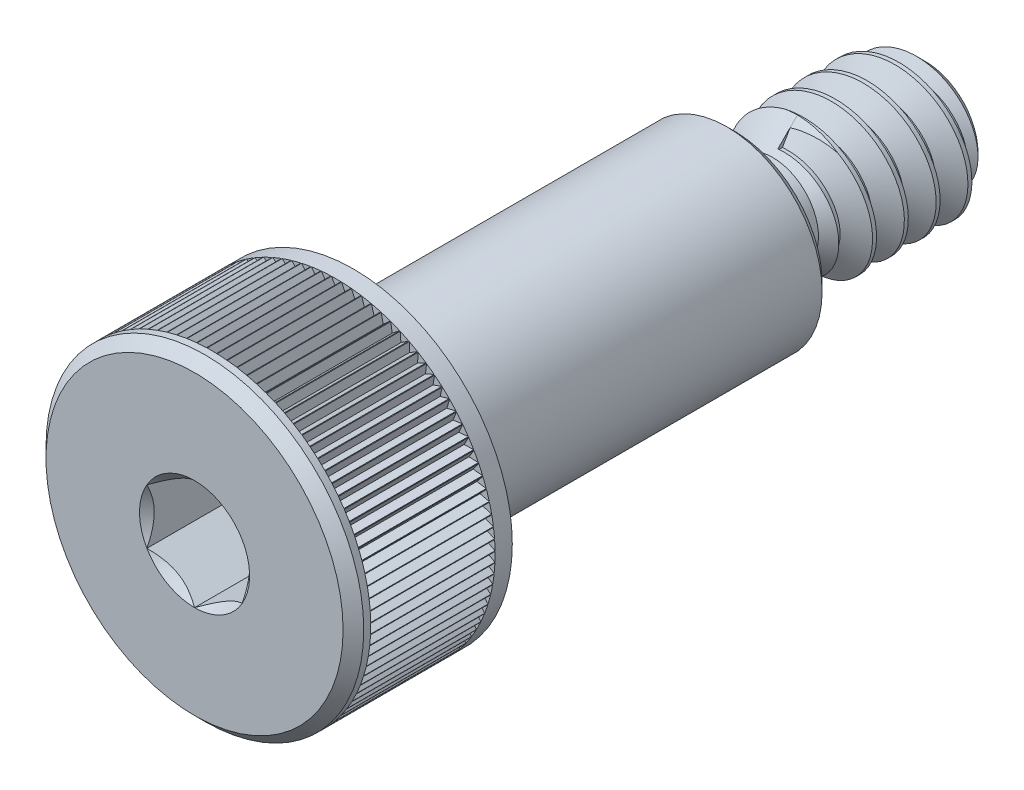
SolidWorks part; units mm, degrees
other "DetailItem1"
other "DetailItem2"
other "DetailItem5"
other "DetailItem6"
ref_plane "Front" through (0, 0, 0) normal (0, 0, 1) x (1, 0, 0)
ref_plane "Top" through (0, 0, 0) normal (0, 1, 0) x (1, 0, 0)
ref_plane "Right" through (0, 0, 0) normal (1, 0, 0) x (0, 0, -1)
sketch "Sketch1" plane through (0, 0, 0) normal (1, 0, 0) x (0, 0, -1)
  line L0 (0, 3.9687) -> (3.9687, 3.9688) construction
  line L1 (3.9687, 3.9688) -> (3.9687, 2.1828) construction
  line L2 (4.9609, 2.3812) -> (13.4938, 2.3812) construction
  line L3 (4.9609, -2.3812) -> (13.4938, -2.3813) construction
  line L4 (13.4938, 1.7526) -> (18.2563, 1.7526) construction
  line L5 (18.2563, 1.7526) -> (18.2563, 0) construction
  line L6 (13.4938, 0) -> (0, 0) construction
  line L7 (0, 0) -> (0, 3.9687) construction
  line L8 (0, 3.9687) -> (0, -3.9688) construction
  line L9 (18.2563, 1.7526) -> (18.2563, -1.7526) construction
  line L10 (13.4938, 2.3812) -> (13.4938, -2.3813) construction
  line L11 (18.2563, -1.7526) -> (16.5785, -1.7526) construction
  line L12 (13.4938, 2.3812) -> (13.4938, 0) construction
  line L13 (3.9687, 2.1828) -> (4.7625, 2.1828) construction
  line L14 (4.7625, 2.1828) -> (4.9609, 2.3812) construction
  line L15 (18.2563, 0) -> (13.4938, 0) construction
  line L16 (4.7625, -2.1828) -> (4.9609, -2.3812) construction
  line L17 (3.9688, -2.1828) -> (4.7625, -2.1828) construction
  line L18 (0, -3.9688) -> (3.9688, -3.9688) construction
  line L19 (3.9688, -3.9688) -> (3.9688, -2.1828) construction
  line L20 (18.2563, 2.3813) -> (17.0656, 2.3813) construction
  line L21 (18.2563, -2.3812) -> (17.0656, -2.3812) construction
  line L22 (18.2563, 0) -> (23.0188, 0) construction
  line L23 (8.7313, 0) -> (8.7313, 3.9688) construction
  line L24 (18.2563, -2.3812) -> (18.2563, 2.3813) construction
  line L25 (0, -1.1906) -> (0, 1.1906) construction
  line L26 (18.2066, 1.8385) -> (19.0004, 1.8385) construction
  line L27 (19.0004, 1.8385) -> (18.6035, 1.1511) construction
  line L28 (18.6035, 1.1511) -> (18.2066, 1.8385) construction
  line L29 (18.6035, 1.1511) -> (18.6035, 1.237) construction
  line L30 (18.6035, 1.8385) -> (18.6035, 1.7526) construction
  line L31 (18.9508, 1.7526) -> (18.2563, 1.7526) construction
  line L32 (18.5539, 1.237) -> (18.6531, 1.237) construction
  line L33 (18.6035, 1.7956) -> (18.9756, 1.7956) construction
  line L34 (18.6035, 1.7956) -> (18.2314, 1.7956) construction
  line L35 (4.9609, 2.3812) -> (4.9609, -2.3812) construction
  line L36 (13.2953, 2.3813) -> (13.4938, 2.1828) construction
  line L37 (13.2953, 2.3813) -> (13.2953, 0) construction
  point P2 (4.2069, 0)
  point P8 (17.0656, -1.7526)
  point P12 (13.4938, 0)
  point P15 (13.2556, 0)
  point P31 (4.6593, 0)
  point P32 (12.8032, 0)
  point P34 (18.2563, 0)
  point P37 (0, 0)
  dimension "Head Dia" = 7.9375
  dimension "Head Ht" = 3.9688
  dimension "Thread Lg" = 4.7625
  dimension "Thread Dia" = 3.5052
  dimension "Shoulder Dia" = 4.7625
  dimension "D1" = 1.1906
  dimension "D2" = 1.6778
  dimension "D3" = 135
  dimension "D4" = 0.7937
  dimension "D5" = 0.1984
  dimension "D6" = 4.7625
  dimension "D7" = 9.0487
  dimension "D8" = 8.1439
  dimension "Hex" = 2.3813
  dimension "Pitch" = 0.7937
  dimension "D9" = 0.0992
  dimension "Shoulder Lg" = 9.525
  dimension "D10" = 45
sketch "Sketch13" plane through (0, 0, 0) normal (1, 0, 0) x (0, 0, -1)
  line L0 (0, 0) -> (0, 3.9687)
  line L1 (0, 3.9687) -> (3.9687, 3.9688)
  line L2 (3.9687, 3.9688) -> (3.9687, 2.1828)
  line L3 (3.9687, 2.1828) -> (4.7625, 2.1828)
  line L4 (13.4938, 0) -> (13.4938, 2.1828)
  line L5 (4.7625, 2.1828) -> (4.9609, 2.3813)
  line L7 (13.4938, 2.3812) -> (13.4938, 0) construction
  line L8 (13.4938, 2.3812) -> (13.4938, -2.3813) construction
  line L9 (13.4938, 0) -> (0, 0) construction
  line L10 (13.4938, 2.1828) -> (13.2953, 2.3812)
  line L12 (4.9609, 2.3813) -> (13.2953, 2.3812)
  line L13 (0, 0) -> (13.4938, 0)
  line L14 (4.9609, 2.3812) -> (13.4938, 2.3812) construction
  line L18 (18.2563, 2.3813) -> (18.2563, -2.3812) construction
  dimension "D1" = 9.525
  dimension "D2" = 45
  dimension "D3" = 4.7625
revolve "Revolve1" add sketch "Sketch13" angle 360 about L9
sketch "Sketch12" plane through (0, 0, -13.4938) normal (0, 0, -1) x (-1, 0, 0)
  circle A0 centre (0, 0) radius 1.7526
extrude "Boss-Extrude1" add sketch "Sketch12" along normal up to vertex (4.7625 mm away) up to point (0, 0, -18.2563)
ref_plane "Plane1" through (0, 0, -18.2563) normal (0, 0, 1) x (1, 0, 0)
sketch "Sketch3" plane through (0, 0, -18.2563) normal (0, 0, 1) x (1, 0, 0)
  circle A0 centre (0, 0) radius 1.7526
sketch "Sketch5" plane through (0, 0, 0) normal (1, 0, 0) x (0, 0, -1)
  line L0 (13.4938, 1.7526) -> (15.0597, 1.7526)
  line L1 (15.0597, 1.7526) -> (14.4463, 1.1392)
  line L2 (14.4463, 1.1392) -> (13.4938, 1.1392)
  line L3 (13.4938, 1.7526) -> (13.4938, 1.1392)
  line L4 (13.4938, 1.7526) -> (18.2563, 1.7526) construction
  line L5 (13.4938, 2.3812) -> (13.4938, 0) construction
  line L6 (13.4938, 2.3812) -> (13.4938, -2.3813) construction
  line L7 (18.2563, 0) -> (13.4938, 0) construction
  line L8 (18.2563, -1.7526) -> (18.2563, 1.7526) construction
  dimension "D4" = 0.9525
  dimension "D1" = 45
  dimension "D2" = 3.81
  dimension "D3" = 1.1392
revolve "Cut-Revolve1" cut sketch "Sketch5" angle 360 mid plane about L6
chamfer "Chamfer1" distance 0.4381 angle 45 1 edges at (-1.7526, 0, -18.2563)
chamfer "Chamfer2" distance 0.258 angle 45 1 edges at (-3.9687, 0, 0)
fillet "Fillet1" radius 0.1984 1 edges at (0, 1.1392, -13.4938)
sketch "Sketch10" plane through (0, 0, 0) normal (1, 0, 0) x (0, 0, -1)
  line L0 (0.258, 0) -> (3.7108, 0) construction
  line L1 (3.9687, -3.9688) -> (3.9687, 3.9688) construction
  line L2 (0.258, -3.9687) -> (0.258, 3.9687) construction
  line L3 (0.258, 0) -> (0, 0) construction
  line L4 (3.7108, 0) -> (3.9687, 0) construction
  point P6 (1.9844, 0)
  dimension "D1" = 3.4528
ref_plane "Plane2" through (0, 0, -1.9844) normal (0, 0, 1) x (1, 0, 0)
sketch "Sketch8" plane through (0, 0, 0) normal (0, 0, 1) x (1, 0, 0)
  line L1 (1.1906, 0.6874) -> (0, 1.3748)
  line L2 (0, 1.3748) -> (-1.1906, 0.6874)
  line L3 (-1.1906, 0.6874) -> (-1.1906, -0.6874)
  line L4 (-1.1906, -0.6874) -> (0, -1.3748)
  line L5 (0, -1.3748) -> (1.1906, -0.6874)
  line L6 (1.1906, -0.6874) -> (1.1906, 0.6874)
  circle A0 centre (0, 0) radius 1.1906 construction
extrude "Cut-Extrude2" cut sketch "Sketch8" against normal blind 1.9844
sketch "Sketch9" plane through (0, 0, 0) normal (0, 0, 1) x (1, 0, 0)
  circle A0 centre (0, 0) radius 1.3748
extrude "Cut-Extrude4" cut sketch "Sketch9" against normal blind 1.9844 draft 45
sketch "Sketch16" plane through (0, 0, 0) normal (0, 1, 0) x (1, 0, 0)
  line L0 (0, 8.7313) -> (-2.3812, 8.7313) construction
  line L1 (-2.3812, 13.2953) -> (-2.3812, 4.9609) construction
  line L2 (0, 12.8032) -> (-2.3812, 12.8032) construction
  line L3 (0, 8.7313) -> (0, 12.8032) construction
  line L4 (0, 10.7672) -> (0, 12.8032) construction
  line L5 (0, 12.8032) -> (0, 11.7852) construction
  line L6 (0, 11.7852) -> (-2.3812, 11.7852) construction
  line L7 (0, 4.9609) -> (-2.3813, 4.9609) construction
  line L8 (-2.3813, 4.9609) -> (2.3813, 4.9609) construction
  line L9 (0, 13.4938) -> (2.3812, 13.4938) construction
  point P0 (0, 8.7313)
  point P2 (0, 12.8032)
  point P11 (0, 4.9609)
sketch "reference 1" plane through (0, 0, -3.9687) normal (0, 0, -1) x (-1, 0, 0)
  circle A1 centre (0, 0) radius 3.9687
ref_axis "Center Axis 1" through (0, 0, -4.9609) along (0, 0, -1)
ref_plane "Contact Plane 1" through (0, 0, -18.2563) normal (0, 0, -1) x (-1, 0, 0)
ref_plane "Contact Plane 2" through (0, 0, -3.9687) normal (0, 0, -1) x (-1, 0, 0)
ref_plane "Plane3" through (0, 0, -13.4938) normal (0, 0, 1) x (1, 0, 0)
split "Split1" trim tools "Plane3" bodies to split 118 resulting bodies 127 128
sketch "Sketch15" plane through (0, 0, -18.2563) normal (0, 0, -1) x (-1, 0, 0)
  circle A0 centre (0, 0) radius 1.7526
curve "Helix/Spiral1" pitch 0.7937 height 3.9688 radius 1.7526 centre (0, 0, -18.2563) axis (0, 0, 1) start towards (0, 1, 0)
sketch "Sketch4" plane through (0, 0, 0) normal (1, 0, 0) x (0, 0, -1)
  line L0 (18.5539, 1.237) -> (18.6531, 1.237) construction
  line L1 (19.0004, 1.8385) -> (18.6035, 1.1511) construction
  line L3 (18.6035, 1.7956) -> (18.9756, 1.7956) construction
  line L4 (18.6035, 1.7956) -> (18.2314, 1.7956) construction
  line L5 (18.6035, 1.1511) -> (18.2066, 1.8385) construction
  line L6 (18.5539, 1.237) -> (18.6531, 1.237)
  line L7 (18.9756, 1.7956) -> (18.6531, 1.237)
  line L8 (18.6035, 1.7956) -> (18.9756, 1.7956)
  line L9 (18.6035, 1.7956) -> (18.2314, 1.7956)
  line L10 (18.5539, 1.237) -> (18.2314, 1.7956)
sweep "Cut-Sweep1" cut profiles "Sketch4" path "Helix/Spiral1" align with end faces yes
sketch "Sketch14" plane through (0, 0, -13.4938) normal (0, 0, -1) x (-1, 0, 0)
  line L0 (0, -2.3812) -> (0, 2.3813) construction
  circle A0 centre (0, 0) radius 0.8763
  dimension "D1" = 1.7526
extrude "Boss-Extrude2" add sketch "Sketch14" along normal up to vertex (3.5719 mm away) up to point (0, 2.3813, -17.0656)
sketch "Sketch11" plane through (0, 0, -1.9844) normal (0, 0, 1) x (1, 0, 0)
  line L0 (0, 3.7624) -> (0, 3.9687) construction
  line L1 (0, 3.7624) -> (0.1192, 3.9687)
  line L2 (0, 3.7624) -> (-0.1192, 3.9687)
  line L3 (-0.1192, 3.9687) -> (0.1192, 3.9687)
  line L4 (0, 0) -> (-0.1192, 3.9687) construction
  line L5 (0.1192, 3.9687) -> (0, 0) construction
  circle A2 centre (0, 0) radius 3.9687 construction
  point P8 (2.3908, 0.7309)
  dimension "D1" = 0.2064
  dimension "D2" = 3.439
extrude "Cut-Extrude5" cut sketch "Sketch11" along normal blind 1.5538 and the other way blind 1.5538
pattern_circular "CirPattern1" count 99 over 360 about axis through (0, 0, -13.4938) along (0, 0, 1) of "Cut-Extrude5" reverse direction yes
equation "\"D1@Chamfer1\" = \"Thread Dia@Sketch1\" * .125"
equation "\"D1@Cut-Extrude2\"= \"Head Ht@Sketch1\" * .5"
equation "\"D1@Cut-Extrude4\" = \"D1@Cut-Extrude2\""
equation "\"D1@Chamfer2\"=\"Head Dia@Sketch1\" * .0325"
equation "\"D1@Sketch1\"=\"Pitch@Sketch1\"*1.5"
equation "\"D1@Sketch11\"=\"D1@Chamfer2\"*.8"
equation "\"D4@Sketch5\"=\"Thread Lg@Sketch1\"*0.2"
equation "\"D3@Sketch5\"=(\"Thread Dia@Sketch1\"*0.65)/2"
equation "\"D1@Fillet1\"=\"Pitch@Sketch1\"*.25"
equation "\"D1@Cut-Extrude5\"=\"D1@Sketch10\"*.45"
equation "\"D1@CirPattern1\"=(360/(\"D2@Sketch11\"))-6"
equation "\"D4@Sketch1\"=\"Head Ht@Sketch1\"*0.2"
equation "\"D5@Sketch1\"=\"Head Dia@Sketch1\"*0.025"
equation "\"D6@Sketch1\"=\"Shoulder Lg@Sketch1\"/2"
equation "\"D7@Sketch1\"=\"Shoulder Lg@Sketch1\"*0.95"
equation "\"D8@Sketch1\"=\"D7@Sketch1\"*0.9"
equation "\"D2@Cut-Extrude5\"=\"D1@Sketch10\"*.45"
equation "\"D9@Sketch1\"=\"Pitch@Sketch1\"/8"
equation "\"D1@Sketch14\"=\"Thread Dia@Sketch1\"*.5"
equation "\"D4@Helix/Spiral1\"=\"Pitch@Sketch1\""
equation "\"D3@Helix/Spiral1\"=\"Thread Lg@Sketch1\"-\"Pitch@Sketch1\""
